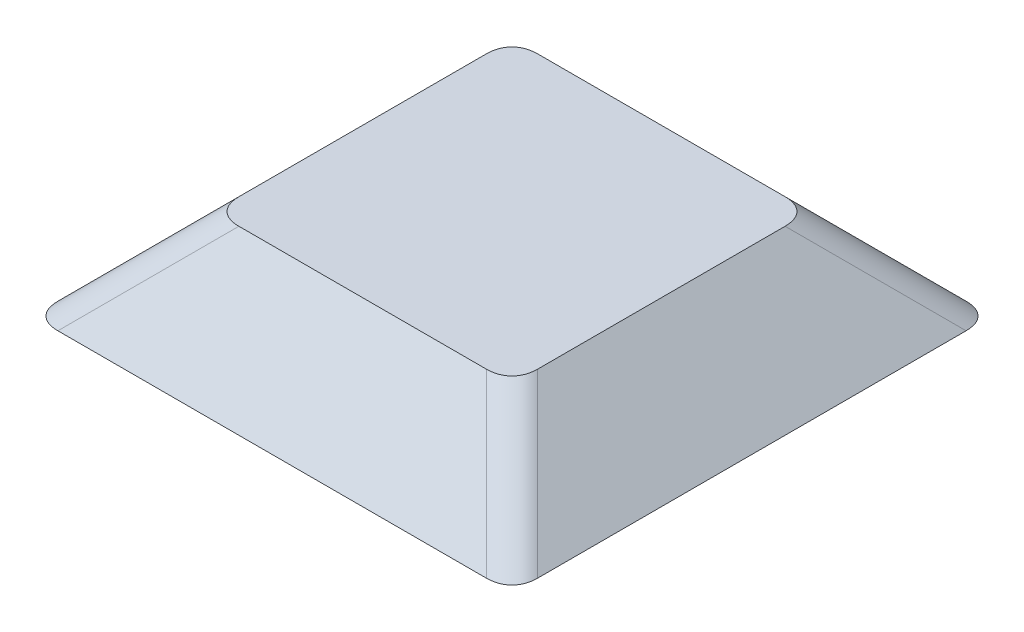
SolidWorks part; units mm, degrees
ref_plane "Front Plane" through (0, 0, 0) normal (0, 0, 1) x (1, 0, 0)
ref_plane "Top Plane" through (0, 0, 0) normal (0, 1, 0) x (1, 0, 0)
ref_plane "Right Plane" through (0, 0, 0) normal (1, 0, 0) x (0, 0, -1)
sketch "Sketch1" plane through (0, 0, 0) normal (0, 1, 0) x (1, 0, 0)
  line L1 (-53, 53) -> (53, 53)
  line L2 (-53, 53) -> (-53, -53)
  line L3 (-53, -53) -> (53, -53)
  line L4 (53, 53) -> (53, -53)
  line L5 (-53, 53) -> (53, -53) construction
  line L6 (-53, -53) -> (53, 53) construction
  point P0 (0, 0)
  dimension "D1" = 106
  dimension "D2" = 106
extrude "Boss-Extrude1" add sketch "Sketch1" along normal blind 20
chamfer "Chamfer3" distance 20 4 edges at (-53, 20, 0) (0, 20, -53) (53, 20, 0) (0, 20, 53)
fillet "Fillet1" radius 8 4 edges at (-43, 10, -43) (43, 10, -43) (43, 10, 43) (-43, 10, 43)
